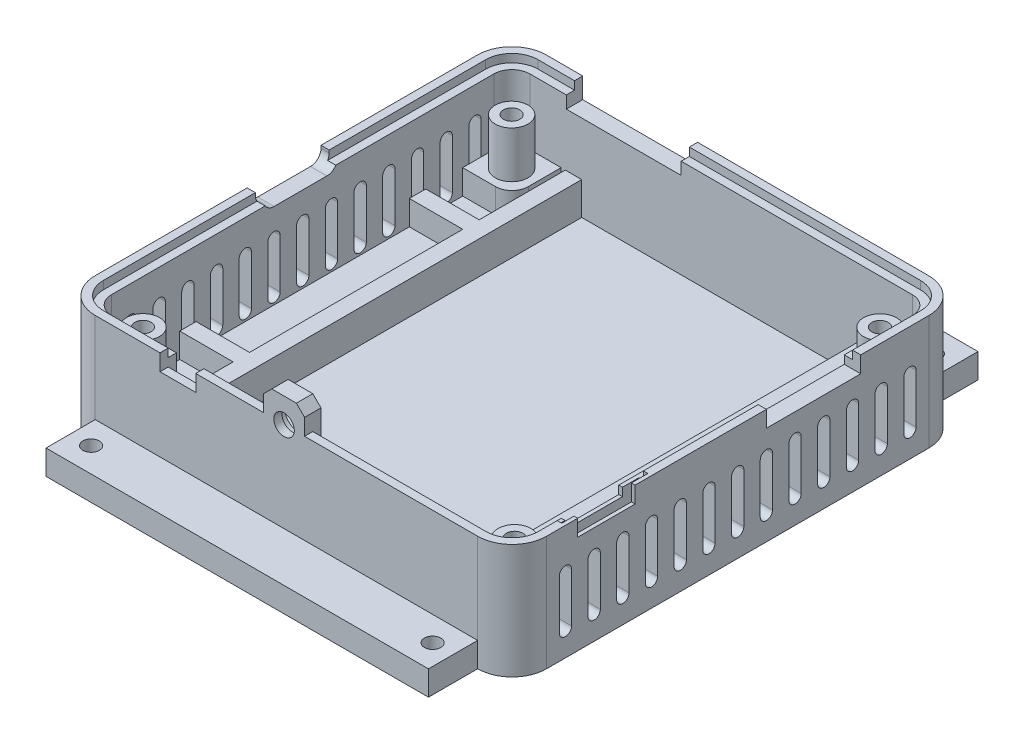
SolidWorks part; units mm, degrees
ref_plane "Front Plane" through (0, 0, 0) normal (0, 0, 1) x (1, 0, 0)
ref_plane "Top Plane" through (0, 0, 0) normal (0, 1, 0) x (1, 0, 0)
ref_plane "Right Plane" through (0, 0, 0) normal (1, 0, 0) x (0, 0, -1)
sketch "Sketch2" plane through (0, 0, 0) normal (0, 1, 0) x (1, 0, 0)
  line L0 (-26.515, 23.3) -> (-26.515, -23.3)
  line L1 (-23.315, 25.5) -> (23.315, 25.5)
  line L2 (-25.515, 23.3) -> (-25.515, -23.3)
  line L3 (-23.315, -25.5) -> (23.315, -25.5)
  line L4 (25.515, 23.3) -> (25.515, -23.3)
  line L5 (-25.515, 25.5) -> (25.515, -25.5) construction
  line L6 (-25.515, -25.5) -> (25.515, 25.5) construction
  line L7 (-23.315, -26.5) -> (23.315, -26.5)
  line L8 (26.515, 23.3) -> (26.515, -23.3)
  line L9 (-23.315, 26.5) -> (23.315, 26.5)
  line L10 (-27.515, 23.3) -> (-27.515, -23.3)
  line L11 (-23.315, -27.5) -> (23.315, -27.5)
  line L12 (27.515, 23.3) -> (27.515, -23.3)
  line L13 (-23.315, 27.5) -> (23.315, 27.5)
  line L14 (-25.515, 19.5) -> (-21.515, 19.5)
  line L15 (-19.515, 21.5) -> (-19.515, 25.5)
  line L16 (19.515, 25.5) -> (19.515, 21.5)
  line L17 (21.515, 19.5) -> (25.515, 19.5)
  line L18 (-25.515, -19.5) -> (-21.515, -19.5)
  line L19 (-19.515, -21.5) -> (-19.515, -25.5)
  line L20 (19.515, -25.5) -> (19.515, -21.5)
  line L21 (21.515, -19.5) -> (25.515, -19.5)
  arc A0 (23.315, 25.5) -> (25.515, 23.3) centre (23.315, 23.3) cw
  arc A1 (25.515, -23.3) -> (23.315, -25.5) centre (23.315, -23.3) cw
  arc A2 (-23.315, -25.5) -> (-25.515, -23.3) centre (-23.315, -23.3) cw
  arc A3 (-23.315, 25.5) -> (-25.515, 23.3) centre (-23.315, 23.3) ccw
  arc A4 (-23.315, -26.5) -> (-26.515, -23.3) centre (-23.315, -23.3) cw
  arc A5 (26.515, -23.3) -> (23.315, -26.5) centre (23.315, -23.3) cw
  arc A6 (23.315, 26.5) -> (26.515, 23.3) centre (23.315, 23.3) cw
  arc A7 (-23.315, 26.5) -> (-26.515, 23.3) centre (-23.315, 23.3) ccw
  arc A8 (-23.315, -27.5) -> (-27.515, -23.3) centre (-23.315, -23.3) cw
  arc A9 (27.515, -23.3) -> (23.315, -27.5) centre (23.315, -23.3) cw
  arc A10 (23.315, 27.5) -> (27.515, 23.3) centre (23.315, 23.3) cw
  arc A11 (-23.315, 27.5) -> (-27.515, 23.3) centre (-23.315, 23.3) ccw
  circle A12 centre (-22.455, 22.41) radius 1
  circle A13 centre (22.445, 22.42) radius 1
  circle A14 centre (22.425, -22.11) radius 1
  circle A15 centre (-22.495, -22.49) radius 1
  arc A20 (21.515, -19.5) -> (19.515, -21.5) centre (21.515, -21.5) ccw
  arc A21 (-19.515, -21.5) -> (-21.515, -19.5) centre (-21.515, -21.5) ccw
  arc A22 (-19.515, 21.5) -> (-21.515, 19.5) centre (-21.515, 21.5) cw
  arc A23 (21.515, 19.5) -> (19.515, 21.5) centre (21.515, 21.5) cw
  point P0 (0, 0)
  point P64 (-20.015, -20)
  point P65 (19.515, -19.5)
  point P67 (20.015, -20)
  point P69 (-19.515, -19.5)
  point P70 (20.015, 20)
  point P73 (-20.015, 20)
  point P74 (-19.515, 19.5)
  point P77 (19.515, 19.5)
  dimension "D3" = 2.2
  dimension "D6" = 3.09
  dimension "D7" = 3.06
  dimension "D8" = 2
  dimension "D9" = 2
  dimension "D10" = 3.07
  dimension "D11" = 3.08
  dimension "D12" = 2
  dimension "D13" = 3.39
  dimension "D14" = 3.09
  dimension "D15" = 3.01
  dimension "D16" = 3.02
  dimension "D17" = 2
  dimension "D28" = 2
  dimension "D29" = 55.03
  dimension "D30" = 55
  dimension "D18" = 6
  dimension "D19" = 6
  dimension "D20" = 6
  dimension "D21" = 6
  dimension "D1" = 51.03
  dimension "D2" = 51
  dimension "D5" = 2
  dimension "D22" = 6
  dimension "D23" = 6
  dimension "D24" = 6
  dimension "D25" = 6
  dimension "D26" = 1
  dimension "D27" = 1
  dimension "D4" = 1
extrude "Boss-Extrude1" add sketch "Sketch2" along normal blind 14 contours L13 A11 L10 A8 L11 A9 L12 A10 A7 L9 A6 L8 A5 L7 A4 L0 region at (-25.7347, 0, -25.7197)
extrude "Boss-Extrude2" add sketch "Sketch2<3>" along normal blind 13 contours L9 A7 L0 A4 L7 A5 L8 A6 A3 L1 A0 L4 A1 L3 A2 L2 region at (-25.0476, 0, -25.0326)
sketch "Sketch2<3>" plane through (0, 0, 0) normal (0, 1, 0) x (1, 0, 0) same geometry as "Sketch2"
extrude "Boss-Extrude4" add sketch "Sketch2<5>" along normal blind 2 contours L2 L3 L4 L1 region at (0, 0, 0)
sketch "Sketch2<5>" plane through (0, 0, 0) normal (0, 1, 0) x (1, 0, 0) same geometry as "Sketch2"
sketch "Sketch4" plane through (0, 0, -27.5) normal (0, 0, -1) x (-1, 0, 0)
  line L0 (23.315, 14) -> (-23.315, 14) construction
  line L1 (18.875, 11.5) -> (4.875, 11.5)
  line L2 (18.875, 11.5) -> (18.875, 14)
  line L3 (18.875, 14) -> (4.875, 14)
  line L4 (4.875, 11.5) -> (4.875, 14)
  line L5 (18.875, 11.5) -> (4.875, 14) construction
  line L6 (18.875, 14) -> (4.875, 11.5) construction
  line L7 (27.515, 14) -> (27.515, 0) construction
  point P0 (11.875, 12.75)
  dimension "D1" = 8.64
  dimension "D2" = 14
  dimension "D3" = 2.5
extrude "Cut-Extrude1" cut sketch "Sketch4" against normal blind 2
sketch "Sketch6" plane through (-27.515, 0, 0) normal (-1, 0, 0) x (0, 0, 1)
  line L0 (-23.3, 14) -> (23.3, 14) construction
  line L1 (-4.225, 14) -> (4.775, 14)
  line L2 (-4.225, 14) -> (-4.225, 13.68)
  line L3 (-2.945, 12.4) -> (3.495, 12.4)
  line L4 (4.775, 14) -> (4.775, 13.68)
  line L5 (-27.5, 14) -> (-27.5, 0) construction
  line L6 (27.5, 14) -> (27.5, 0) construction
  arc A0 (4.775, 13.68) -> (3.495, 12.4) centre (3.495, 13.68) cw
  arc A1 (-2.945, 12.4) -> (-4.225, 13.68) centre (-2.945, 13.68) cw
  point P10 (4.775, 12.4)
  point P13 (-4.225, 12.4)
  dimension "D4" = 1.28
  dimension "D1" = 23.275
  dimension "D2" = 1.6
  dimension "D3" = 9
  dimension "D5" = 22.725
extrude "Cut-Extrude3" cut sketch "Sketch6" against normal blind 2
sketch "Sketch7" plane through (0, 0, 27.5) normal (0, 0, 1) x (1, 0, 0)
  line L0 (-23.315, 0) -> (23.315, 0) construction
  line L1 (27.515, 14) -> (27.515, 0) construction
  line L2 (0, 0) -> (0, 27.9568) construction
  line L3 (-27.515, 14) -> (-27.515, 0) construction
  circle A0 centre (-0.29, 13.97) radius 1.25
  dimension "D1" = 27.225
  dimension "D2" = 2.5
  dimension "D3" = 13.97
  dimension "D4" = 27.805
extrude "Cut-Extrude4" cut sketch "Sketch7" against normal blind 2
sketch "Sketch8" plane through (0, 0, 25.5) normal (0, 0, -1) x (-1, 0, 0)
  circle A0 centre (0.29, 13.97) radius 2
  dimension "D1" = 4
sketch "Sketch9" plane through (0, 2, 0) normal (0, 1, 0) x (1, 0, 0)
  line L0 (-17, 25.5) -> (-17, -25.5)
  line L1 (-19.515, 25.5) -> (19.515, 25.5) construction
  line L2 (-19.515, -25.5) -> (19.515, -25.5) construction
  line L3 (17, 25.5) -> (17, -25.5)
  line L4 (-25.515, 19.5) -> (-25.515, -19.5) construction
  line L5 (25.515, 19.5) -> (25.515, -19.5) construction
  line L6 (-19, 25.5) -> (-19, 15)
  line L7 (19, 25.5) -> (19, 15)
  line L8 (-19, 25.5) -> (-17, 25.5)
  line L9 (-19, -25.5) -> (-17, -25.5)
  line L10 (17, -25.5) -> (19, -25.5)
  line L11 (17, 25.5) -> (19, 25.5)
  line L13 (-25.515, 19.5) -> (-25.515, -19.5) construction
  line L14 (-25.515, 15) -> (-19, 15)
  line L15 (-25.515, 15) -> (-25.515, 13)
  line L16 (-25.515, 13) -> (-19, 13)
  line L17 (25.515, 15) -> (25.515, 13)
  line L18 (25.515, 23.3) -> (25.515, -23.3) construction
  line L19 (-25.515, -4.5794) -> (-25.515, -23.3) construction
  line L20 (-25.515, -13) -> (-19, -13)
  line L21 (-25.515, -13) -> (-25.515, -15)
  line L22 (-25.515, -15) -> (-19, -15)
  line L23 (25.515, -13) -> (25.515, -15)
  line L24 (19, 15) -> (25.515, 15)
  line L25 (19, 13) -> (25.515, 13)
  line L26 (19, -13) -> (25.515, -13)
  line L27 (19, -15) -> (25.515, -15)
  line L28 (-19.515, 25.5) -> (19.515, 25.5) construction
  line L29 (-19.515, -25.5) -> (19.515, -25.5) construction
  line L30 (-4.875, 25.5) -> (23.315, 25.5) construction
  line L31 (-19, 13) -> (-19, -13)
  line L32 (-19, 25.5) -> (-19, -25.5) construction
  line L33 (-19, -15) -> (-19, -25.5)
  line L34 (19, -15) -> (19, -25.5)
  line L35 (19, 25.5) -> (19, -25.5) construction
  line L36 (19, 13) -> (19, -13)
  dimension "D1" = 34
  dimension "D2" = 8.515
  dimension "D3" = 8.515
  dimension "D6" = 2
  dimension "D7" = 2
  dimension "D8" = 2
  dimension "D9" = 2
  dimension "D10" = 10.5
  dimension "D11" = 10.5
  dimension "D12" = 26
  dimension "D13" = 10.5
  dimension "D14" = 26
  dimension "D15" = 10.5
  dimension "D4" = 2
  dimension "D5" = 2
extrude "Boss-Extrude6" add sketch "Sketch9" along normal blind 3
extrude "Boss-Extrude9" add sketch "Sketch2<7>" along normal blind 5 contours A12 | A13 | A15 | A14 region at (-21.415, 0, -25.4151) region at (21.415, 0, -25.4151) region at (-23.515, 0, 19.5849) region at (25.4301, 0, 21.4)
sketch "Sketch2<7>" plane through (0, 0, 0) normal (0, 1, 0) x (1, 0, 0) same geometry as "Sketch2"
sketch "Sketch11" plane through (0, 5, 0) normal (0, 1, 0) x (1, 0, 0)
  circle A0 centre (-22.455, 22.41) radius 1
  circle A1 centre (-22.455, 22.41) radius 2
  circle A2 centre (22.445, 22.42) radius 1
  circle A3 centre (22.445, 22.42) radius 2
  circle A6 centre (-22.495, -22.49) radius 1
  circle A7 centre (-22.495, -22.49) radius 2
  circle A8 centre (22.425, -22.11) radius 1
  circle A9 centre (22.425, -22.11) radius 2
  dimension "D1" = 2
  dimension "D2" = 4
  dimension "D3" = 2
  dimension "D4" = 4
  dimension "D5" = 2
  dimension "D6" = 4
  dimension "D7" = 2
  dimension "D8" = 4
extrude "Boss-Extrude10" add sketch "Sketch11" along normal blind 5.68
sketch "Sketch13" plane through (0, 0, 27.5) normal (0, 0, 1) x (1, 0, 0)
  line L0 (27.515, 14) -> (27.515, 0) construction
  line L5 (-27.515, 14) -> (-27.515, 0) construction
  line L7 (0.9596, 14) -> (23.315, 14) construction
  line L8 (-2.79, 17) -> (2.21, 17)
  line L9 (-2.79, 17) -> (-2.79, 14)
  line L10 (-2.79, 14) -> (-1.5396, 14)
  line L11 (2.21, 17) -> (2.21, 14)
  line L12 (-2.79, 17) -> (2.21, 14) construction
  line L13 (-2.79, 14) -> (2.21, 17) construction
  line L14 (0.9596, 14) -> (2.21, 14)
  arc A0 (0.9596, 14) -> (-1.5396, 14) centre (-0.29, 13.97) ccw
  point P0 (-0.29, 15.5)
  dimension "D4" = 0.03
  dimension "D5" = 2.5
  dimension "D7" = 2.5
  dimension "D1" = 5
  dimension "D2" = 25.305
  dimension "D3" = 3
  dimension "D6" = 24.725
extrude "Boss-Extrude11" add sketch "Sketch13" against normal blind 2
sketch "Sketch15" plane through (0, 0, 26.5) normal (0, 0, -1) x (-1, 0, 0)
  line L0 (-1.459, 13) -> (-1.459, 14)
  line L1 (-2.21, 14) -> (-2.21, 13)
  line L2 (-2.21, 13) -> (-1.459, 13)
  line L3 (-1.459, 14) -> (-2.21, 14)
  line L4 (2.039, 13) -> (2.039, 14)
  line L5 (2.79, 14) -> (2.79, 13)
  line L6 (2.039, 14) -> (2.79, 14)
  line L7 (2.79, 13) -> (2.039, 13)
  dimension "D1" = 1
  dimension "D2" = 1
  dimension "D3" = 0.751
  dimension "D4" = 1
  dimension "D5" = 1
  dimension "D6" = 0.751
extrude "Boss-Extrude13" add sketch "Sketch15" along normal blind 1
extrude "Cut-Extrude5" cut sketch "Sketch8" against normal blind 1
sketch "Sketch16" plane through (0, 2, 0) normal (0, 1, 0) x (1, 0, 0)
  line L1 (-17, 25.5) -> (17, 25.5)
  line L2 (-17, 25.5) -> (-17, -25.5)
  line L3 (-17, -25.5) -> (17, -25.5)
  line L4 (17, 25.5) -> (17, -25.5)
  line L5 (-17, 25.5) -> (17, -25.5) construction
  line L6 (-17, -25.5) -> (17, 25.5) construction
  point P0 (0, 0)
extrude "Cut-Extrude6" cut sketch "Sketch16" against normal blind 1
sketch "Sketch17" plane through (0, 0, 0) normal (0, -1, 0) x (1, 0, 0)
  circle A0 centre (-22.495, 22.49) radius 2
  circle A1 centre (22.425, 22.11) radius 2
  circle A2 centre (-22.455, -22.41) radius 2
  circle A3 centre (22.445, -22.42) radius 2
  dimension "D1" = 4
  dimension "D2" = 4
  dimension "D3" = 4
  dimension "D4" = 4
extrude "Cut-Extrude7" cut sketch "Sketch17" against normal blind 4
sketch "Sketch19" plane through (27.515, 0, 0) normal (1, 0, 0) x (0, 0, -1)
  line L0 (23.3, 14) -> (-23.3, 14) construction
  line L2 (-21.75, 9) -> (-21.75, 3)
  line L4 (-20.25, 9) -> (-20.25, 3)
  line L5 (-27.5, 14) -> (-27.5, 0) construction
  line L6 (23.3, 0) -> (-23.3, 0) construction
  line L7 (-18.25, 9) -> (-18.25, 3)
  line L8 (-16.75, 9) -> (-16.75, 3)
  line L9 (-14.75, 9) -> (-14.75, 3)
  line L10 (-13.25, 9) -> (-13.25, 3)
  line L11 (-11.25, 9) -> (-11.25, 3)
  line L12 (-9.75, 9) -> (-9.75, 3)
  line L13 (-7.75, 9) -> (-7.75, 3)
  line L14 (-6.25, 9) -> (-6.25, 3)
  line L15 (-4.25, 9) -> (-4.25, 3)
  line L16 (-2.75, 9) -> (-2.75, 3)
  line L17 (-0.75, 9) -> (-0.75, 3)
  line L18 (0.75, 9) -> (0.75, 3)
  line L19 (2.75, 9) -> (2.75, 3)
  line L20 (4.25, 9) -> (4.25, 3)
  line L21 (6.25, 9) -> (6.25, 3)
  line L22 (7.75, 9) -> (7.75, 3)
  line L23 (9.75, 9) -> (9.75, 3)
  line L24 (11.25, 9) -> (11.25, 3)
  line L25 (13.25, 9) -> (13.25, 3)
  line L26 (14.75, 9) -> (14.75, 3)
  line L27 (16.75, 9) -> (16.75, 3)
  line L28 (18.25, 9) -> (18.25, 3)
  line L29 (20.25, 9) -> (20.25, 3)
  line L30 (21.75, 9) -> (21.75, 3)
  line L31 (27.5, 14) -> (27.5, 0) construction
  arc A0 (-21.75, 9) -> (-20.25, 9) centre (-21, 9) cw
  arc A1 (-21.75, 3) -> (-20.25, 3) centre (-21, 3) ccw
  arc A2 (-18.25, 3) -> (-16.75, 3) centre (-17.5, 3) ccw
  arc A3 (-18.25, 9) -> (-16.75, 9) centre (-17.5, 9) cw
  arc A4 (-14.75, 3) -> (-13.25, 3) centre (-14, 3) ccw
  arc A5 (-14.75, 9) -> (-13.25, 9) centre (-14, 9) cw
  arc A6 (-11.25, 3) -> (-9.75, 3) centre (-10.5, 3) ccw
  arc A7 (-11.25, 9) -> (-9.75, 9) centre (-10.5, 9) cw
  arc A8 (-7.75, 3) -> (-6.25, 3) centre (-7, 3) ccw
  arc A9 (-7.75, 9) -> (-6.25, 9) centre (-7, 9) cw
  arc A10 (-4.25, 3) -> (-2.75, 3) centre (-3.5, 3) ccw
  arc A11 (-4.25, 9) -> (-2.75, 9) centre (-3.5, 9) cw
  arc A12 (-0.75, 3) -> (0.75, 3) centre (0, 3) ccw
  arc A13 (-0.75, 9) -> (0.75, 9) centre (0, 9) cw
  arc A14 (2.75, 3) -> (4.25, 3) centre (3.5, 3) ccw
  arc A15 (2.75, 9) -> (4.25, 9) centre (3.5, 9) cw
  arc A16 (6.25, 3) -> (7.75, 3) centre (7, 3) ccw
  arc A17 (6.25, 9) -> (7.75, 9) centre (7, 9) cw
  arc A18 (9.75, 3) -> (11.25, 3) centre (10.5, 3) ccw
  arc A19 (9.75, 9) -> (11.25, 9) centre (10.5, 9) cw
  arc A20 (13.25, 3) -> (14.75, 3) centre (14, 3) ccw
  arc A21 (13.25, 9) -> (14.75, 9) centre (14, 9) cw
  arc A22 (16.75, 3) -> (18.25, 3) centre (17.5, 3) ccw
  arc A23 (16.75, 9) -> (18.25, 9) centre (17.5, 9) cw
  arc A24 (20.25, 3) -> (21.75, 3) centre (21, 3) ccw
  arc A25 (20.25, 9) -> (21.75, 9) centre (21, 9) cw
  dimension "D3" = 0.75
  dimension "D1" = 6
  dimension "D2" = 1.5
  dimension "D4" = 5
  dimension "D5" = 5.75
  dimension "D6" = 3
  dimension "D8" = 5.75
  dimension "D7" = 13
extrude "Cut-Extrude9" cut sketch "Sketch19" against normal blind 2
sketch "Sketch20" plane through (-27.515, 0, 0) normal (-1, 0, 0) x (0, 0, 1)
  line L0 (-23.3, 14) -> (-4.225, 14) construction
  line L2 (-21.75, 9) -> (-21.75, 3)
  line L4 (-20.25, 9) -> (-20.25, 3)
  line L5 (-23.3, 0) -> (23.3, 0) construction
  line L6 (-27.5, 14) -> (-27.5, 0) construction
  line L7 (-18.25, 9) -> (-18.25, 3)
  line L8 (-16.75, 9) -> (-16.75, 3)
  line L9 (-14.75, 9) -> (-14.75, 3)
  line L10 (-13.25, 9) -> (-13.25, 3)
  line L11 (-11.25, 9) -> (-11.25, 3)
  line L12 (-9.75, 9) -> (-9.75, 3)
  line L13 (-7.75, 9) -> (-7.75, 3)
  line L14 (-6.25, 9) -> (-6.25, 3)
  line L15 (-4.25, 9) -> (-4.25, 3)
  line L16 (-2.75, 9) -> (-2.75, 3)
  line L17 (-0.75, 9) -> (-0.75, 3)
  line L18 (0.75, 9) -> (0.75, 3)
  line L19 (2.75, 9) -> (2.75, 3)
  line L20 (4.25, 9) -> (4.25, 3)
  line L21 (6.25, 9) -> (6.25, 3)
  line L22 (7.75, 9) -> (7.75, 3)
  line L23 (9.75, 9) -> (9.75, 3)
  line L24 (11.25, 9) -> (11.25, 3)
  line L25 (13.25, 9) -> (13.25, 3)
  line L26 (14.75, 9) -> (14.75, 3)
  line L27 (16.75, 9) -> (16.75, 3)
  line L28 (18.25, 9) -> (18.25, 3)
  line L29 (20.25, 9) -> (20.25, 3)
  line L30 (21.75, 9) -> (21.75, 3)
  line L31 (27.5, 14) -> (27.5, 0) construction
  arc A0 (-21.75, 9) -> (-20.25, 9) centre (-21, 9) cw
  arc A1 (-21.75, 3) -> (-20.25, 3) centre (-21, 3) ccw
  arc A2 (-18.25, 3) -> (-16.75, 3) centre (-17.5, 3) ccw
  arc A3 (-18.25, 9) -> (-16.75, 9) centre (-17.5, 9) cw
  arc A4 (-14.75, 3) -> (-13.25, 3) centre (-14, 3) ccw
  arc A5 (-14.75, 9) -> (-13.25, 9) centre (-14, 9) cw
  arc A6 (-11.25, 3) -> (-9.75, 3) centre (-10.5, 3) ccw
  arc A7 (-11.25, 9) -> (-9.75, 9) centre (-10.5, 9) cw
  arc A8 (-7.75, 3) -> (-6.25, 3) centre (-7, 3) ccw
  arc A9 (-7.75, 9) -> (-6.25, 9) centre (-7, 9) cw
  arc A10 (-4.25, 3) -> (-2.75, 3) centre (-3.5, 3) ccw
  arc A11 (-4.25, 9) -> (-2.75, 9) centre (-3.5, 9) cw
  arc A12 (-0.75, 3) -> (0.75, 3) centre (0, 3) ccw
  arc A13 (-0.75, 9) -> (0.75, 9) centre (0, 9) cw
  arc A14 (2.75, 3) -> (4.25, 3) centre (3.5, 3) ccw
  arc A15 (2.75, 9) -> (4.25, 9) centre (3.5, 9) cw
  arc A16 (6.25, 3) -> (7.75, 3) centre (7, 3) ccw
  arc A17 (6.25, 9) -> (7.75, 9) centre (7, 9) cw
  arc A18 (9.75, 3) -> (11.25, 3) centre (10.5, 3) ccw
  arc A19 (9.75, 9) -> (11.25, 9) centre (10.5, 9) cw
  arc A20 (13.25, 3) -> (14.75, 3) centre (14, 3) ccw
  arc A21 (13.25, 9) -> (14.75, 9) centre (14, 9) cw
  arc A22 (16.75, 3) -> (18.25, 3) centre (17.5, 3) ccw
  arc A23 (16.75, 9) -> (18.25, 9) centre (17.5, 9) cw
  arc A24 (20.25, 3) -> (21.75, 3) centre (21, 3) ccw
  arc A25 (20.25, 9) -> (21.75, 9) centre (21, 9) cw
  dimension "D1" = 1.5
  dimension "D2" = 6
  dimension "D3" = 5
  dimension "D4" = 3
  dimension "D5" = 5.75
  dimension "D7" = 5.75
  dimension "D6" = 13
extrude "Cut-Extrude10" cut sketch "Sketch20" against normal blind 2
sketch "Sketch21" plane through (0, 0, 27.5) normal (0, 0, 1) x (1, 0, 0)
  line L0 (-23.315, 14) -> (-2.79, 14) construction
  line L1 (-15.415, 14) -> (-11.055, 14)
  line L2 (-15.415, 14) -> (-15.415, 12)
  line L3 (-15.415, 12) -> (-11.055, 12)
  line L4 (-11.055, 14) -> (-11.055, 12)
  line L5 (-27.515, 14) -> (-27.515, 0) construction
  dimension "D1" = 12.1
  dimension "D2" = 4.36
  dimension "D3" = 2
extrude "Cut-Extrude11" cut sketch "Sketch21" against normal blind 2
sketch "Sketch23" plane through (0, 0, 25.5) normal (0, 0, -1) x (-1, 0, 0)
  line L1 (11.055, 12) -> (15.415, 12)
  line L2 (11.055, 12) -> (11.055, 5.5)
  line L3 (11.055, 5.5) -> (15.415, 5.5)
  line L4 (15.415, 12) -> (15.415, 5.5)
  dimension "D1" = 4.36
  dimension "D2" = 6.5
extrude "Cut-Extrude12" cut sketch "Sketch23" against normal blind 1
sketch "Sketch24" plane through (27.515, 0, 0) normal (1, 0, 0) x (0, 0, -1)
  line L0 (23.3, 14) -> (-23.3, 14) construction
  line L1 (-19.5, 14) -> (-12.5, 14)
  line L2 (-19.5, 14) -> (-19.5, 12)
  line L3 (-19.5, 12) -> (-12.5, 12)
  line L4 (-12.5, 14) -> (-12.5, 12)
  line L5 (-27.5, 14) -> (-27.5, 0) construction
  line L6 (27.5, 14) -> (27.5, 0) construction
  line L7 (3.5, 14) -> (15, 14)
  line L8 (3.5, 14) -> (3.5, 12)
  line L9 (3.5, 12) -> (15, 12)
  line L10 (15, 14) -> (15, 12)
  dimension "D1" = 2
  dimension "D2" = 7
  dimension "D3" = 8
  dimension "D4" = 2
  dimension "D5" = 12.5
  dimension "D6" = 11.5
extrude "Cut-Extrude13" cut sketch "Sketch24" against normal blind 2
sketch "Sketch26" plane through (0, 14, 0) normal (0, 1, 0) x (1, 0, 0)
  line L0 (27.515, -12.5) -> (26.515, -12.5) construction
  line L1 (25.965, -10.5) -> (27.065, -10.5)
  line L2 (25.965, -10.5) -> (25.965, -21)
  line L3 (25.965, -21) -> (27.065, -21)
  line L4 (27.065, -10.5) -> (27.065, -21)
  line L5 (25.515, -19.5) -> (26.515, -19.5) construction
  line L6 (25.515, 23.3) -> (25.515, 15) construction
  line L7 (27.515, 23.3) -> (27.515, 15) construction
  dimension "D1" = 2
  dimension "D2" = 1.1
  dimension "D3" = 10.5
  dimension "D4" = 1.5
  dimension "D5" = 0.45
  dimension "D6" = 0.45
extrude "Cut-Extrude14" cut sketch "Sketch26" against normal blind 4
chamfer "Chamfer1" distance 1 angle 45 2 edges at (-2.79, 17, 26.5) (2.21, 17, 26.5)
sketch "Sketch28" plane through (0, 0, 27.5) normal (0, 0, 1) x (1, 0, 0)
  line L5 (23.315, 14) -> (23.315, 0) construction
  line L6 (-23.315, 0) -> (23.315, 0)
  line L7 (-23.315, 0) -> (-23.315, 3)
  line L8 (-23.315, 3) -> (23.315, 3)
  line L9 (23.315, 0) -> (23.315, 3)
  dimension "D1" = 3
extrude "Boss-Extrude14" add sketch "Sketch28" along normal blind 6
sketch "Sketch29" plane through (0, 0, -27.5) normal (0, 0, -1) x (-1, 0, 0)
  line L0 (23.315, 14) -> (23.315, 0) construction
  line L1 (-23.315, 0) -> (23.315, 0)
  line L2 (-23.315, 0) -> (-23.315, 3)
  line L3 (-23.315, 3) -> (23.315, 3)
  line L4 (23.315, 0) -> (23.315, 3)
  dimension "D1" = 3
extrude "Boss-Extrude15" add sketch "Sketch29" along normal blind 6
sketch "Sketch30" plane through (0, 3, 0) normal (0, 1, 0) x (1, 0, 0)
  line L0 (-23.315, -33.5) -> (-23.315, -27.5) construction
  line L1 (-23.315, 33.5) -> (-23.315, 27.5) construction
  line L2 (-23.315, 33.5) -> (23.315, 33.5) construction
  line L5 (23.315, 33.5) -> (23.315, 27.5) construction
  line L6 (23.315, -33.5) -> (23.315, -27.5) construction
  line L7 (23.315, -33.5) -> (-23.315, -33.5) construction
  circle A0 centre (-20.815, -30.5) radius 1
  circle A1 centre (20.815, -30.5) radius 1
  circle A2 centre (-20.815, 30.5) radius 1
  circle A3 centre (20.815, 30.5) radius 1
  dimension "D1" = 2
  dimension "D2" = 2
  dimension "D3" = 2
  dimension "D4" = 2
  dimension "D5" = 2.5
  dimension "D6" = 2.5
  dimension "D7" = 3
  dimension "D8" = 2.5
  dimension "D9" = 3
  dimension "D10" = 2.5
  dimension "D11" = 3
  dimension "D12" = 3
extrude "Cut-Extrude15" cut sketch "Sketch30" against normal blind 3
